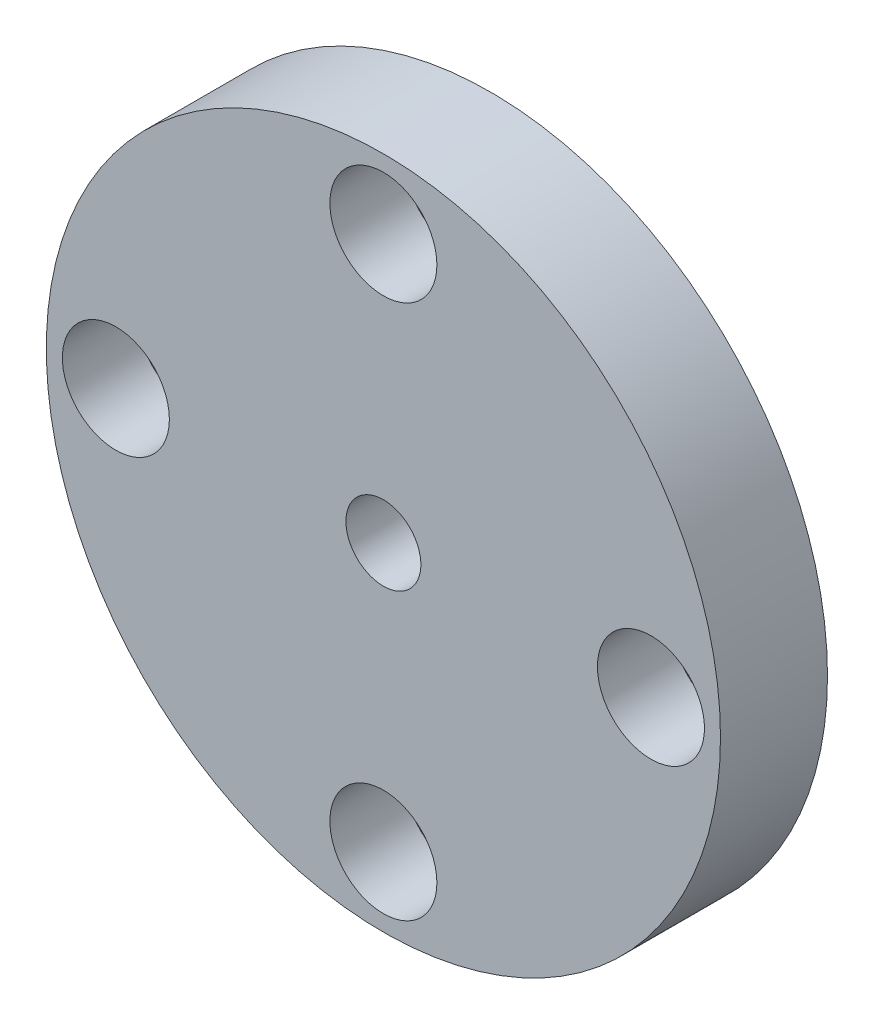
SolidWorks part; units mm, degrees
ref_plane "Front Plane" through (0, 0, 0) normal (0, 0, 1) x (1, 0, 0)
ref_plane "Top Plane" through (0, 0, 0) normal (0, 1, 0) x (1, 0, 0)
ref_plane "Right Plane" through (0, 0, 0) normal (1, 0, 0) x (0, 0, -1)
sketch "Sketch1" plane through (0, 0, 0) normal (0, 0, 1) x (1, 0, 0)
  circle A0 centre (0, 0) radius 31.5
  circle A1 centre (0, 0) radius 15.5
  dimension "D1" = 63
  dimension "D2" = 31
extrude "Boss-Extrude1" add sketch "Sketch1" along normal blind 10 contours A1 | A0 A1 region at (-30.609, 0, 0) region at (0, 0, 0)
extrude "Boss-Extrude2" add sketch "Sketch1<3>" against normal blind 4 contours A1 region at (0, 0, 0)
sketch "Sketch1<3>" plane through (0, 0, 0) normal (0, 0, 1) x (1, 0, 0) same geometry as "Sketch1"
sketch "Sketch2" plane through (0, 0, -4) normal (0, 0, -1) x (-1, 0, 0)
  circle A0 centre (0, 0) radius 3.5
  dimension "D1" = 7
extrude "Cut-Extrude1" cut sketch "Sketch2" against normal through all contours A0
sketch "Sketch3" plane through (0, 0, 10) normal (0, 0, 1) x (1, 0, 0)
  line L0 (0, 0) -> (0, 25) construction
  line L1 (0, 0) -> (-25, 0) construction
  circle A0 centre (0, 0) radius 25
  circle A1 centre (-25, 0) radius 5
  circle A2 centre (-25, 0) radius 3
  circle A4 centre (25, 0) radius 5
  circle A5 centre (25, 0) radius 3
  circle A6 centre (0, 25) radius 5
  circle A7 centre (0, 25) radius 3
  circle A8 centre (0, -25) radius 5
  circle A9 centre (0, -25) radius 3
  dimension "D1" = 50
  dimension "D3" = 10
  dimension "D4" = 6
  dimension "D5" = 10
  dimension "D6" = 6
  dimension "D2" = 25
extrude "Cut-Extrude2" cut sketch "Sketch3" against normal blind 7 contours A2 A0 A1 | A2 A0 A1 | A7 A0 A6 | A7 A0 A6 | A0 A5 A4 | A0 A9 A8 | A0 A9 A8 | A4 region at (21.8894, 0, 10) region at (0, 20.1106, 10) region at (4.0062, 24.7925, 10) region at (4.8797, -24.7554, 10) region at (3.9703, -24.5707, 10) region at (-21.3739, 3.2799, 10) region at (-24.7925, 4.0062, 10)
extrude "Cut-Extrude3" cut sketch "Sketch3<4>" against normal through all both and the other way through all contours A0 A2 | A0 A2 | A0 A7 | A0 A7 | A5 A0 | A5 A0 | A9 A0 | A9 A0 region at (23.6949, 0, 10) region at (26.2403, 0, 10) region at (0, 23.6949, 10) region at (0, 26.2403, 10) region at (0, -26.2403, 10) region at (0, -23.6949, 10) region at (-23.6949, 0, 10) region at (-26.2403, 0, 10)
sketch "Sketch3<4>" plane through (0, 0, 10) normal (0, 0, 1) x (1, 0, 0) same geometry as "Sketch3"
